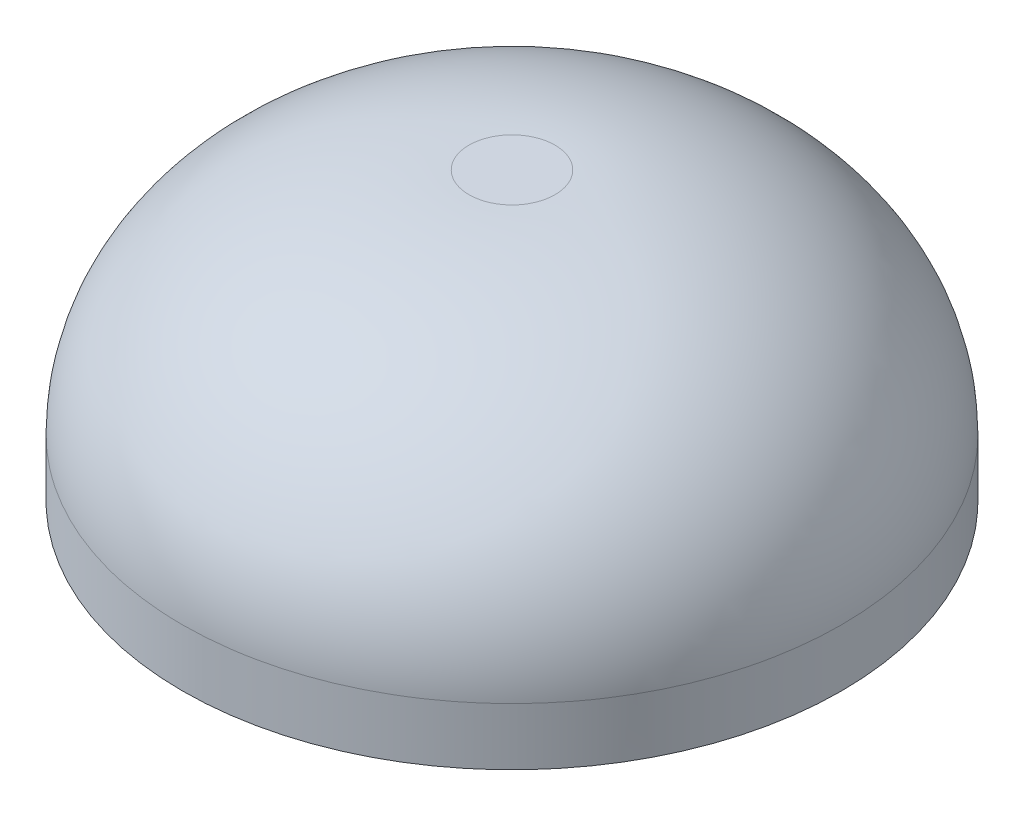
SolidWorks part; units mm, degrees
ref_plane "Front Plane" through (0, 0, 0) normal (0, 0, 1) x (1, 0, 0)
ref_plane "Top Plane" through (0, 0, 0) normal (0, 1, 0) x (1, 0, 0)
ref_plane "Right Plane" through (0, 0, 0) normal (1, 0, 0) x (0, 0, -1)
sketch "Sketch1" plane through (0, 0, 0) normal (0, 1, 0) x (1, 0, 0)
  circle A0 centre (0, 0) radius 11.5
  dimension "D1" = 23
extrude "Boss-Extrude1" add sketch "Sketch1" along normal blind 10
fillet "Fillet1" radius 8 1 edges at (0, 10, 11.5) second distance 10 first distance on face at (0, 10, 11.5)
sketch "Sketch2" plane through (0, 0, 0) normal (0, -1, 0) x (1, 0, 0)
  line L0 (6.347, 0) -> (-6.347, 0) construction
  line L1 (2.95, 1.7032) -> (0, 3.4064)
  line L2 (0, 3.4064) -> (-2.95, 1.7032)
  line L3 (-2.95, 1.7032) -> (-2.95, -1.7032)
  line L4 (-2.95, -1.7032) -> (0, -3.4064)
  line L5 (0, -3.4064) -> (2.95, -1.7032)
  line L6 (2.95, -1.7032) -> (2.95, 1.7032)
  circle A0 centre (0, 0) radius 2.95 construction
  circle A1 centre (0, 0) radius 7
  dimension "D2" = 14
  dimension "D1" = 2.95
extrude "Cut-Extrude1" cut sketch "Sketch2" against normal blind 7 contours A1 L6 L5 L4 L3 L2 L1 region at (-6.802, 0, 0)
sketch "Sketch3" plane through (0, 0, 0) normal (0, -1, 0) x (1, 0, 0)
  circle A0 centre (0, 0) radius 4.5582
extrude "Cut-Extrude2" cut sketch "Sketch3" against normal blind 2.5 contours A0
ref_plane "Plane1" through (0, 0, 15) normal (0, 0, 1) x (1, 0, 0)
sketch "Sketch5" plane through (0, 0, 15) normal (0, 0, 1) x (1, 0, 0)
  line L1 (2.5, -1.5) -> (-2.5, -1.5)
  line L2 (2.5, -1.5) -> (2.5, 1.5)
  line L3 (2.5, 1.5) -> (-2.5, 1.5)
  line L4 (-2.5, -1.5) -> (-2.5, 1.5)
  line L5 (2.5, -1.5) -> (-2.5, 1.5) construction
  line L6 (2.5, 1.5) -> (-2.5, -1.5) construction
  point P0 (0, 0)
  dimension "D1" = 3
  dimension "D2" = 5
